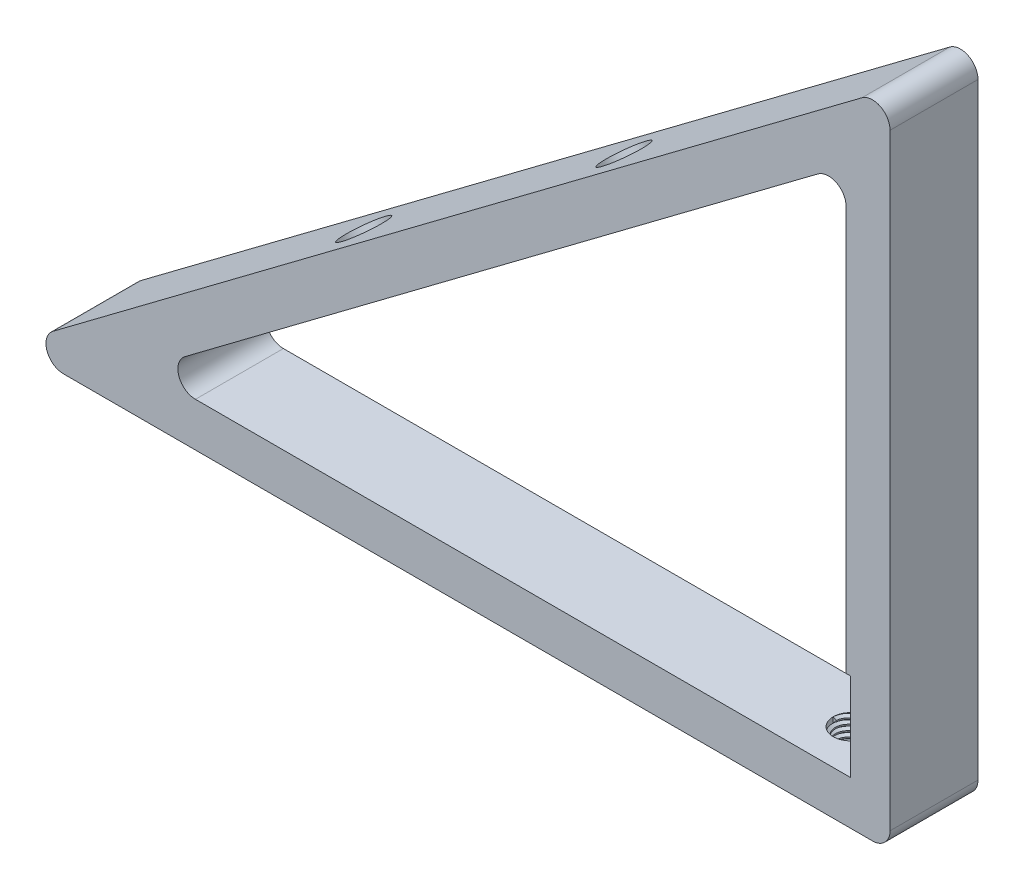
SolidWorks part; units mm, degrees
material "Magnesium Alloy"
ref_plane "Front Plane" through (0, 0, 0) normal (0, 0, 1) x (1, 0, 0)
ref_plane "Top Plane" through (0, 0, 0) normal (0, 1, 0) x (1, 0, 0)
ref_plane "Right Plane" through (0, 0, 0) normal (1, 0, 0) x (0, 0, -1)
sketch "Sketch1" plane through (0, 0, 0) normal (0, 0, 1) x (1, 0, 0)
  line L0 (7.62, 0) -> (124.46, 0)
  line L1 (127, 2.54) -> (127, 90.17)
  line L2 (122.936, 92.202) -> (6.096, 4.572)
  arc A0 (127, 2.54) -> (124.46, 0) centre (124.46, 2.54) cw
  arc A1 (127, 90.17) -> (122.936, 92.202) centre (124.46, 90.17) ccw
  arc A2 (7.62, 0) -> (6.096, 4.572) centre (7.62, 2.54) cw
  point P6 (127, 0)
  point P9 (127, 95.25)
  point P12 (0, 0)
  dimension "D3" = 2.54
  dimension "D1" = 127
  dimension "D2" = 95.25
extrude "Boss-Extrude1" add sketch "Sketch1" along normal blind 12.7
sketch "Sketch2" plane through (0, 0, 0) normal (0, 0, 1) x (1, 0, 0)
  line L2 (116.586, 79.502) -> (25.146, 10.922)
  line L5 (120.65, 6.35) -> (26.67, 6.35)
  line L6 (120.65, 6.35) -> (120.65, 77.47)
  line L8 (127, 2.54) -> (127, 90.17) construction
  line L9 (7.62, 0) -> (124.46, 0) construction
  line L10 (122.936, 92.202) -> (6.096, 4.572) construction
  arc A1 (120.65, 77.47) -> (116.586, 79.502) centre (118.11, 77.47) ccw
  arc A2 (25.146, 10.922) -> (26.67, 6.35) centre (26.67, 8.89) ccw
  point P9 (120.65, 6.35)
  dimension "D5" = 93.98
  dimension "D3" = 2.54
  dimension "D6" = 6.35
  dimension "D4" = 71.12
  dimension "D7" = 6.35
  dimension "D8" = 114.3
extrude "Cut-Extrude1" cut sketch "Sketch2" along normal through all
hole_wizard "Ø5.0mm Dowel Hole1" positions "Sketch3" profile "Sketch5" hole size "Ø5.0" standard "ANSI Metric"
sketch "Sketch3" plane through (0, 0, 0) normal (0, -1, 0) x (-1, 0, 0)
  line L0 (-124.46, -12.7) -> (-124.46, 0) construction
  line L1 (-7.62, -12.7) -> (-124.46, -12.7) construction
  point P0 (-114.935, -6.35)
  dimension "D1" = 9.525
  dimension "D2" = 6.35
sketch "Sketch5" plane through (114.935, 0, 6.35) normal (1, 0, 0) x (0, 0, -1)
  line L0 (0, 0) -> (0, 7.8522)
  line L1 (0, 7.8522) -> (2.5, 6.35)
  line L2 (2.5, 6.35) -> (2.5, 0)
  line L5 (2.5, 0) -> (0, 0)
  line L10 (0, 7.8522) -> (-2.5, 6.35) construction
  line L11 (0, -6.35) -> (0, 107.95) construction
  dimension "Hole Dia." = 5
  dimension "Hole Depth" = 6.35
  dimension "Drill Angle" = 118
thread "Thread1" pitch 0.8 method extrude profile "Thread Profile1" start angle 0, offset 0, length 5.6515, pitch 0.8, diameter 5
ref_plane "Plane1" through (112.435, 6.35, 6.35) normal (0, 0, 1) x (-1, 0, 0)
sketch "Thread Profile1" plane through (112.435, 6.35, 6.35) normal (0, 0, 1) x (-1, 0, 0)
  line L0 (0, 0) -> (0, 0.8) construction
  line L11 (0, 0) -> (0, 0.7)
  line L12 (0, 0.7) -> (-0.433, 0.45)
  line L13 (-0.433, 0.45) -> (-0.433, 0.25)
  line L15 (-0.433, 0.25) -> (0, 0)
  line L17 (-0.433, 0.35) -> (0, 0.35) construction
  point P2 (0, 0)
  dimension "Pitch" = 0.8
  dimension "Profile_Angle" = 60
  dimension "Profile_Land" = 0.2
  dimension "Profile_Height" = 0.433
hole_wizard "1/4 (0.25) Diameter Hole1" positions "Sketch6" profile "Sketch7" hole size "1/4" standard "ANSI Inch"
sketch "Sketch6" plane through (0, 0, 0) normal (-0.6, 0.8, 0) x (0.8, 0.6, 0)
  line L0 (153.67, 0) -> (7.62, 0) construction
  line L1 (7.62, -12.7) -> (7.62, 0) construction
  point P0 (55.7773, -6.35)
  point P2 (102.7673, -6.35)
  dimension "D1" = 6.35
  dimension "D2" = 6.35
  dimension "D3" = 48.1573
  dimension "D4" = 46.99
sketch "Sketch7" plane through (44.6218, 33.4664, 6.35) normal (0, 0, 1) x (-0.8, -0.6, 0)
  line L0 (0, 0) -> (0, 8.2577)
  line L1 (0, 8.2577) -> (3.175, 6.35)
  line L2 (3.175, 6.35) -> (3.175, 0)
  line L5 (3.175, 0) -> (0, 0)
  line L10 (0, 8.2577) -> (-3.175, 6.35) construction
  line L11 (0, -6.35) -> (0, 107.95) construction
  dimension "Hole Dia." = 6.35
  dimension "Hole Depth" = 6.35
  dimension "Drill Angle" = 118
sketch "Sketch8" plane through (0, 0, 12.7) normal (0, 0, 1) x (1, 0, 0)
  line L0 (120.65, 6.35) -> (121.285, 6.35)
  line L1 (121.285, 6.35) -> (121.285, 19.05)
  line L2 (121.285, 19.05) -> (120.65, 19.05)
  line L3 (120.65, 6.35) -> (120.65, 77.47) construction
  line L4 (120.65, 19.05) -> (120.65, 6.35)
  line L5 (127, 2.54) -> (127, 90.17) construction
  dimension "D1" = 5.715
  dimension "D2" = 12.7
extrude "Cut-Extrude2" cut sketch "Sketch8" against normal up to surface (12.7 mm away) up to face at (85.7697, 31.6108, 0)
